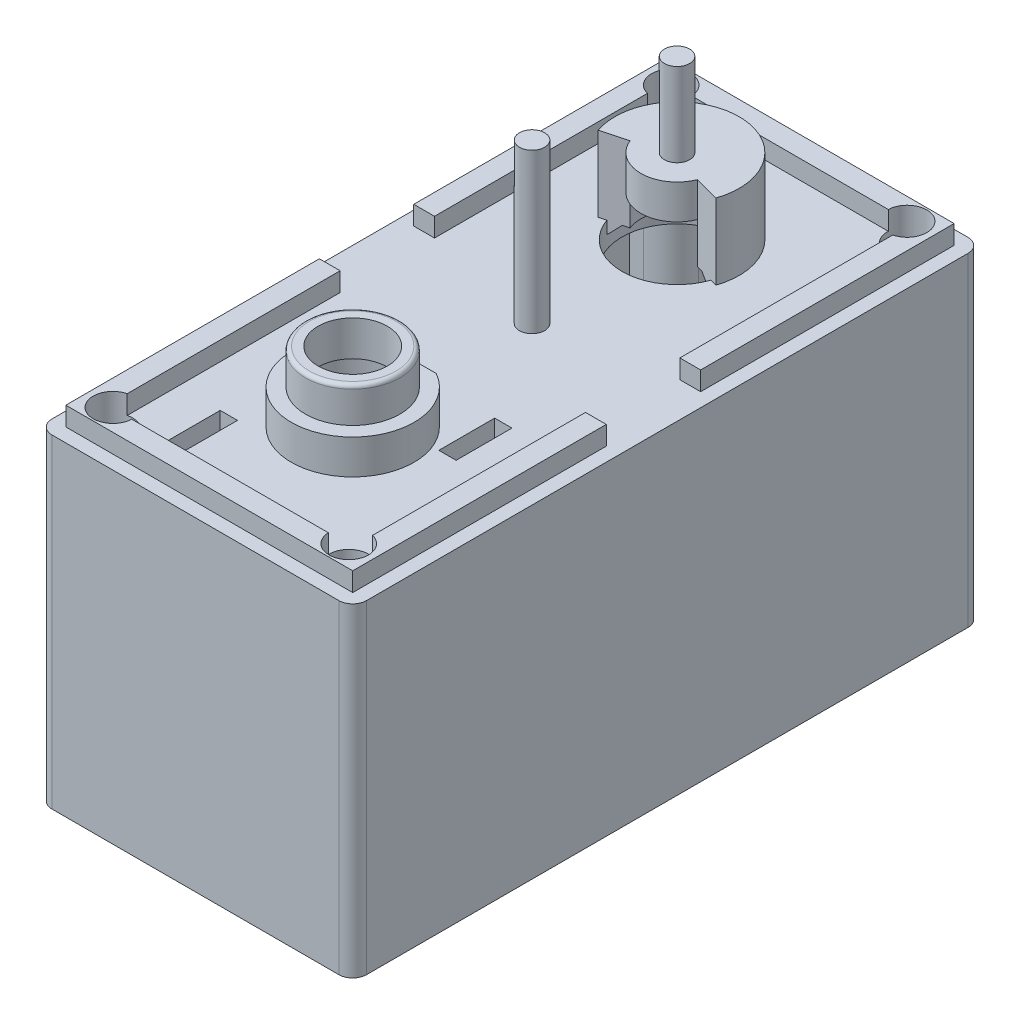
SolidWorks part; units mm, degrees
ref_plane "Front Plane" through (0, 0, 0) normal (0, 0, 1) x (1, 0, 0)
ref_plane "Top Plane" through (0, 0, 0) normal (0, 1, 0) x (1, 0, 0)
ref_plane "Right Plane" through (0, 0, 0) normal (1, 0, 0) x (0, 0, -1)
sketch "Sketch1" plane through (0, 0, 0) normal (0, 1, 0) x (1, 0, 0)
  line L0 (0, 0) -> (4, 0) construction
  line L5 (-9.12, 20) -> (9.12, 20)
  line L6 (-10, 19.12) -> (-10, -19.12)
  line L7 (-9.12, -20) -> (9.12, -20)
  line L8 (10, 19.12) -> (10, -19.12)
  line L9 (-10, 20) -> (10, -20) construction
  line L10 (-10, -20) -> (10, 20) construction
  line L11 (0, 0) -> (0, -4) construction
  arc A4 (-9.12, 20) -> (-10, 19.12) centre (-9.12, 19.12) ccw
  arc A5 (9.12, 20) -> (10, 19.12) centre (9.12, 19.12) cw
  arc A6 (9.12, -20) -> (10, -19.12) centre (9.12, -19.12) ccw
  arc A7 (-9.12, -20) -> (-10, -19.12) centre (-9.12, -19.12) cw
  point P0 (0, 0)
  dimension "D3" = 0.88
  dimension "D1" = 20
  dimension "D2" = 40
  dimension "D4" = 0.88
extrude "Boss-Extrude1" add sketch "Sketch1" along normal blind 20.6
sketch "Sketch26" plane through (0, 0, 0) normal (0, -1, 0) x (1, 0, 0)
  line L1 (-9.12, 19.12) -> (9.12, 19.12)
  line L2 (-9.12, 19.12) -> (-9.12, -19.12)
  line L3 (-9.12, -19.12) -> (9.12, -19.12)
  line L4 (9.12, 19.12) -> (9.12, -19.12)
  line L8 (-10, -19.12) -> (-10, 19.12) construction
  line L9 (9.12, -20) -> (-9.12, -20) construction
  line L10 (10, 19.12) -> (10, -19.12) construction
  line L11 (-9.12, 20) -> (9.12, 20) construction
  dimension "D1" = 0.88
  dimension "D2" = 0.88
  dimension "D3" = 0.88
  dimension "D4" = 0.88
extrude "Cut-Extrude9" cut sketch "Sketch26" against normal blind 19
sketch "Sketch2" plane through (0, 20.6, 0) normal (0, 1, 0) x (1, 0, 0)
  line L16 (-7.8, -3) -> (-7.8, -17.8)
  line L17 (-9.12, 3) -> (-7.8, 3)
  line L19 (-9.12, -3) -> (-7.8, -3)
  line L21 (-9.12, 19.12) -> (9.12, 19.12)
  line L22 (-9.12, 19.12) -> (-9.12, 3)
  line L23 (-9.12, -19.12) -> (9.12, -19.12)
  line L24 (9.12, 19.12) -> (9.12, 3)
  line L25 (-7.8, 17.8) -> (7.8, 17.8)
  line L26 (-7.8, 17.8) -> (-7.8, 3)
  line L27 (-7.8, -17.8) -> (7.8, -17.8)
  line L28 (7.8, 17.8) -> (7.8, 3)
  line L33 (-9.12, -3) -> (-9.12, -19.12)
  line L34 (9.12, 20) -> (-9.12, 20) construction
  line L35 (7.8, 3) -> (9.12, 3)
  line L36 (7.8, -3) -> (9.12, -3)
  line L37 (7.8, -3) -> (7.8, -17.8)
  line L38 (9.12, -3) -> (9.12, -19.12)
  line L39 (-10, 19.12) -> (-10, -19.12) construction
  line L40 (10, -19.12) -> (10, 19.12) construction
  line L41 (-9.12, -20) -> (9.12, -20) construction
  point P16 (0, 0)
  point P22 (0, -20)
  dimension "D1" = 0.88
  dimension "D2" = 0.88
  dimension "D3" = 0.88
  dimension "D4" = 0.88
  dimension "D5" = 2.2
  dimension "D6" = 2.2
  dimension "D7" = 2.2
  dimension "D8" = 2.2
  dimension "D9" = 6
extrude "Boss-Extrude2" add sketch "Sketch2" along normal blind 1.2
sketch "Sketch3" plane through (0, 19, 0) normal (0, -1, 0) x (1, 0, 0)
  line L1 (-9.12, -19.12) -> (9.12, -19.12) construction
  circle A0 centre (0, -10.62) radius 3.5
  dimension "D1" = 7
  dimension "D2" = 8.5
extrude "Cut-Extrude1" cut sketch "Sketch3" against normal up to next
sketch "Sketch7" plane through (0, 19, 0) normal (0, -1, 0) x (1, 0, 0)
  line L0 (-10, -19.12) -> (-10, 19.12) construction
  line L1 (-8.4, 18.4) -> (8.4, 18.4)
  line L2 (-8.4, 18.4) -> (-8.4, -18.4)
  line L3 (-8.4, -18.4) -> (8.4, -18.4)
  line L4 (8.4, 18.4) -> (8.4, -18.4)
  line L5 (10, 19.12) -> (10, -19.12) construction
  line L6 (9.12, -20) -> (-9.12, -20) construction
  line L7 (-9.12, 20) -> (9.12, 20) construction
  line L13 (-9.12, 19.12) -> (9.12, 19.12)
  line L14 (-9.12, 19.12) -> (-9.12, -19.12)
  line L15 (-9.12, -19.12) -> (9.12, -19.12)
  line L16 (9.12, 19.12) -> (9.12, -19.12)
  dimension "D1" = 1.6
  dimension "D2" = 1.6
  dimension "D3" = 1.6
  dimension "D4" = 1.6
extrude "Boss-Extrude3" add sketch "Sketch7" along normal blind 16.6
sketch "Sketch28" plane through (0, 19, 0) normal (0, -1, 0) x (1, 0, 0)
  line L0 (9.12, -20) -> (-9.12, -20) construction
  line L1 (-10, -19.12) -> (-10, 19.12) construction
  line L8 (0, 0) -> (4.0662, 0) construction
  line L9 (0, 0) -> (0, -3.8973) construction
  line L38 (-7.5, -16) -> (-9.12, -16)
  line L40 (-9.12, 19.12) -> (-9.12, -19.12) construction
  line L42 (-9.12, -16) -> (-9.12, -19.12)
  line L43 (-9.12, -19.12) -> (-5.75, -19.12)
  line L44 (-9.12, -19.12) -> (9.12, -19.12) construction
  line L45 (-5.75, -19.12) -> (-5.75, -17.75)
  line L46 (5.75, -19.12) -> (5.75, -17.75)
  line L47 (9.12, -19.12) -> (5.75, -19.12)
  line L48 (9.12, -16) -> (9.12, -19.12)
  line L49 (7.5, -16) -> (9.12, -16)
  line L50 (7.5, 16) -> (9.12, 16)
  line L51 (9.12, 16) -> (9.12, 19.12)
  line L52 (9.12, 19.12) -> (5.75, 19.12)
  line L53 (5.75, 19.12) -> (5.75, 17.75)
  line L54 (-5.75, 19.12) -> (-5.75, 17.75)
  line L55 (-9.12, 19.12) -> (-5.75, 19.12)
  line L56 (-9.12, 16) -> (-9.12, 19.12)
  line L57 (-7.5, 16) -> (-9.12, 16)
  circle A16 centre (-7.5, -17.75) radius 1.75 construction
  arc A17 (-5.75, -17.75) -> (-7.5, -16) centre (-7.5, -17.75) ccw
  circle A18 centre (7.5, -17.75) radius 1.75 construction
  arc A19 (5.75, -17.75) -> (7.5, -16) centre (7.5, -17.75) cw
  circle A20 centre (7.5, 17.75) radius 1.75 construction
  circle A21 centre (-7.5, 17.75) radius 1.75 construction
  arc A22 (5.75, 17.75) -> (7.5, 16) centre (7.5, 17.75) ccw
  arc A23 (-5.75, 17.75) -> (-7.5, 16) centre (-7.5, 17.75) cw
  dimension "D1" = 3.5
  dimension "D3" = 2.5
  dimension "D2" = 2.25
extrude "Boss-Extrude13" add sketch "Sketch28" along normal blind 17.9
ref_plane "Plane1" through (0, 1.1, 0) normal (0, -1, 0) x (-1, 0, 0)
sketch "Sketch29" plane through (0, 1.1, 0) normal (0, -1, 0) x (-1, 0, 0)
  line L0 (9.12, -20) -> (-9.12, -20) construction
  line L1 (-10, -19.12) -> (-10, 19.12) construction
  line L2 (0, 0) -> (4, 0) construction
  line L3 (0, 0) -> (0, -4) construction
  circle A0 centre (-7.5, -17.75) radius 1.25
  circle A1 centre (7.5, -17.75) radius 1.25
  circle A2 centre (7.5, 17.75) radius 1.25
  circle A3 centre (-7.5, 17.75) radius 1.25
  dimension "D1" = 2.5
  dimension "D2" = 2.25
  dimension "D3" = 2.5
extrude "Cut-Extrude13" cut sketch "Sketch29" against normal through all
sketch "Sketch5" plane through (0, 19, 0) normal (0, -1, 0) x (1, 0, 0)
  line L0 (9.12, -20) -> (-9.12, -20) construction
  line L3 (-8.4, -5) -> (-6.377, -5)
  line L4 (6.377, -5) -> (8.4, -5)
  line L5 (7.0218, -3.5) -> (8.4, -3.5)
  line L6 (-8.4, -3.5) -> (-7.0218, -3.5)
  line L7 (8.4, -5) -> (8.4, -3.5)
  line L8 (-8.4, -3.5) -> (-8.4, -5)
  arc A0 (6.377, -5) -> (-6.377, -5) centre (0, -10.62) ccw construction
  arc A1 (6.377, -5) -> (-6.377, -5) centre (0, -10.62) ccw
  arc A2 (7.0218, -3.5) -> (-7.0218, -3.5) centre (0, -10.62) ccw
  point P3 (-8.4, -5)
  point P4 (8.4, -5)
  dimension "D1" = 17
  dimension "D2" = 15
  dimension "D3" = 15
  dimension "D4" = 1.5
extrude "Boss-Extrude5" add sketch "Sketch5" along normal blind 10
fillet "Fillet2" radius 0.5 8 edges at (-7.7109, 9, -3.5) (0, 9, -0.62) (7.7109, 9, -3.5) (8.4, 9, -4.25) (7.3885, 9, -5) (0, 9, -2.12) (-7.3885, 9, -5) (-8.4, 9, -4.25)
sketch "Sketch10" plane through (0, 20.6, 0) normal (0, 1, 0) x (1, 0, 0)
  line L0 (-3.7398, 9.3485) -> (-2.14, 9.7771)
  line L2 (3.7398, 9.3485) -> (2.14, 9.7771)
  line L3 (0, 10.62) -> (0, 5.1464) construction
  arc A2 (-2.14, 9.7771) -> (2.14, 9.7771) centre (0, 10.62) ccw
  arc A3 (3.7398, 9.3485) -> (-3.7398, 9.3485) centre (0, 10.62) ccw
  circle A4 centre (0, 10.62) radius 0.8
  dimension "D1" = 4.6
  dimension "D2" = 7.9
  dimension "D5" = 1.6
  dimension "D3" = 4.28
  dimension "D4" = 75
extrude "Boss-Extrude6" add sketch "Sketch10" along normal blind 4.8
sketch "Sketch11" plane through (0, 20.6, 0) normal (0, -1, 0) x (1, 0, 0)
  circle A0 centre (0, -10.62) radius 2.3
extrude "Cut-Extrude3" cut sketch "Sketch11" against normal blind 2.6
chamfer "Chamfer1" distance 0.8 angle 45 1 edges at (0, 20.6, -14.12)
sketch "Sketch12" plane through (0, 23.2, 0) normal (0, -1, 0) x (1, 0, 0)
  circle A0 centre (0, -10.62) radius 0.8
extrude "Boss-Extrude7" add sketch "Sketch12" against normal blind 7.5
sketch "Sketch15" plane through (0, 19, 0) normal (0, -1, 0) x (1, 0, 0)
  line L1 (-5.375, 18.4) -> (-5.125, 18.4)
  line L2 (-5.375, 18.4) -> (-5.375, 4.65)
  line L3 (-5.375, 4.65) -> (5.375, 4.65)
  line L4 (5.375, 18.4) -> (5.375, 4.65)
  line L5 (5.125, 18.4) -> (5.375, 18.4)
  line L7 (-5.125, 18.4) -> (-5.125, 5)
  line L8 (-5.125, 5) -> (5.125, 5)
  line L9 (5.125, 18.4) -> (5.125, 5)
  line L10 (-2.25, 18.4) -> (-1.75, 18.4)
  line L11 (-2.25, 18.4) -> (-2.25, 15.9)
  line L12 (-2.25, 15.9) -> (-1.75, 15.9)
  line L13 (-1.75, 18.4) -> (-1.75, 15.9)
  line L15 (1.75, 18.4) -> (2.25, 18.4)
  line L16 (1.75, 18.4) -> (1.75, 15.9)
  line L17 (1.75, 15.9) -> (2.25, 15.9)
  line L18 (2.25, 18.4) -> (2.25, 15.9)
  dimension "D1" = 13.75
  dimension "D2" = 10.75
  dimension "D3" = 10.25
  dimension "D4" = 13.4
  dimension "D5" = 10.9
  dimension "D6" = 0.5
  dimension "D7" = 3.5
  dimension "D8" = 2.875
  dimension "D9" = 2.875
extrude "Boss-Extrude8" add sketch "Sketch15" along normal blind 3.6
fillet "Fillet3" radius 0.25 2 edges at (-5.375, 17.2, 4.65) (5.375, 17.2, 4.65)
sketch "Sketch21" plane through (0, 19, 0) normal (0, -1, 0) x (1, 0, 0)
  line L1 (-5.125, 16.85) -> (-4.025, 16.85)
  line L2 (-5.125, 16.85) -> (-5.125, 13.3)
  line L3 (-5.125, 13.3) -> (-4.025, 13.3)
  line L4 (-4.025, 16.85) -> (-4.025, 13.3)
  line L5 (5.125, 5) -> (4.025, 5)
  line L6 (5.125, 5) -> (5.125, 8.55)
  line L7 (5.125, 8.55) -> (4.025, 8.55)
  line L8 (4.025, 5) -> (4.025, 8.55)
  line L9 (-5.125, 5) -> (-5.125, 18.4) construction
  line L10 (1.75, 18.4) -> (-1.75, 18.4) construction
  dimension "D1" = 1.55
  dimension "D2" = 3.55
  dimension "D3" = 1.1
  dimension "D4" = 1.1
  dimension "D5" = 3.55
extrude "Cut-Extrude7" cut sketch "Sketch21" against normal up to next
sketch "Sketch20" plane through (0, 20.6, 0) normal (0, 1, 0) x (1, 0, 0)
  line L0 (1.9105, -6.6) -> (-1.9105, -6.6)
  line L2 (-9.12, -20) -> (9.12, -20) construction
  arc A4 (-1.9105, -6.6) -> (1.9105, -6.6) centre (0, -10) ccw
  circle A5 centre (0, -10) radius 3.4 construction
  point P6 (0, -6.6)
  dimension "D1" = 10
extrude "Boss-Extrude10" add sketch "Sketch20" along normal blind 2.2
sketch "Sketch22" plane through (0, 22.8, 0) normal (0, 1, 0) x (1, 0, 0)
  circle A0 centre (0, -10) radius 3
  circle A1 centre (0, -10) radius 2.2
  dimension "D1" = 6
  dimension "D2" = 4.4
extrude "Boss-Extrude11" add sketch "Sketch22" along normal blind 2.25
fillet "Fillet5" radius 0.25 1 edges at (0, 25.05, 13)
sketch "Sketch25" plane through (0, 19, 0) normal (0, -1, 0) x (1, 0, 0)
  line L0 (-3.1975, 12.7232) -> (-3.1975, 7.2768)
  line L1 (3.1975, 12.7232) -> (3.1975, 7.2768)
  arc A0 (-3.1975, 7.2768) -> (3.1975, 7.2768) centre (0, 10) ccw
  arc A2 (3.1975, 12.7232) -> (-3.1975, 12.7232) centre (0, 10) ccw
  circle A3 centre (0, 10) radius 3
  point P5 (-2.9975, 9.8785)
  point P8 (-3.2, 9.8784)
  point P11 (3.2, 9.8784)
  point P12 (2.9975, 9.8785)
  dimension "D1" = 1.2
  dimension "D4" = 6
  dimension "D2" = 0.2
  dimension "D3" = 0.2
extrude "Boss-Extrude12" add sketch "Sketch25" along normal blind 1.8
sketch "Sketch23" plane through (0, 22.8, 0) normal (0, 1, 0) x (1, 0, 0)
  circle A0 centre (0, -10) radius 3
extrude "Cut-Extrude8" cut sketch "Sketch23" against normal through all
sketch "Sketch30" plane through (0, 20.6, 0) normal (0, 1, 0) x (1, 0, 0)
  circle A0 centre (0, 1.4) radius 0.8
  circle A2 centre (0, -10) radius 2.2 construction
  dimension "D1" = 1.6
  dimension "D2" = 11.4
extrude "Boss-Extrude14" add sketch "Sketch30" along normal blind 10.1
